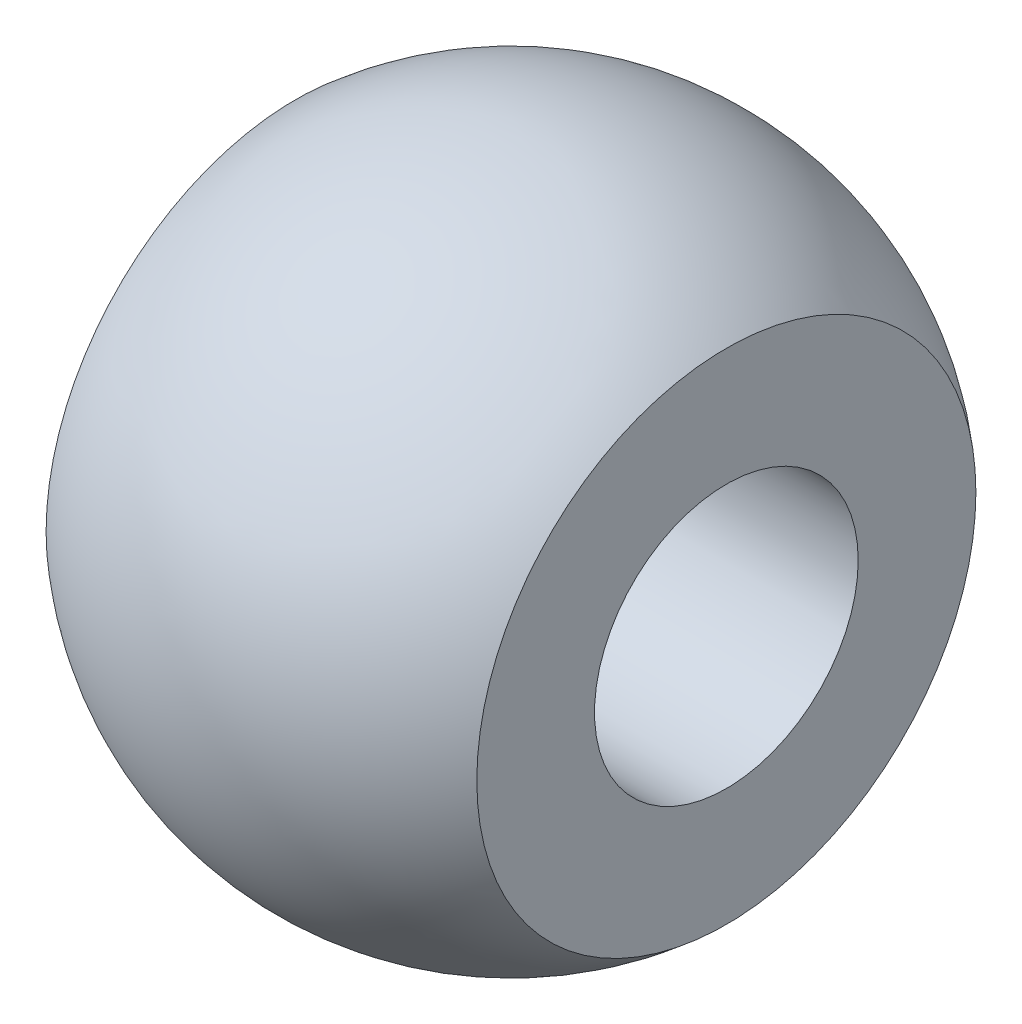
SolidWorks part; units mm, degrees
ref_plane "Front" through (0, 0, 0) normal (0, 0, 1) x (1, 0, 0)
ref_plane "Top" through (0, 0, 0) normal (0, 1, 0) x (1, 0, 0)
ref_plane "Right" through (0, 0, 0) normal (1, 0, 0) x (0, 0, -1)
sketch "Sketch4" plane through (0, 0, 0) normal (1, 0, 0) x (0, 0, -1)
  line L0 (-3.4269, 1.5227) -> (3.4269, -1.5227)
  arc A0 (-3.4269, 1.5227) -> (3.4269, -1.5227) centre (0, 0) ccw
  dimension "D1" = 7.5
revolve "Revolve1" add sketch "Sketch4" angle 360 about L0
sketch "Sketch5" plane through (0, 0, 0) normal (0, 1, 0) x (1, 0, 0)
  line L0 (0, -5.173) -> (0, 6.106) construction
  line L1 (-7.0321, 4.9864) -> (-2.45, 4.9864)
  line L2 (-7.0321, 4.9864) -> (-7.0321, -5.173)
  line L3 (-7.0321, -5.173) -> (-2.45, -5.173)
  line L4 (-2.45, 4.9864) -> (-2.45, -5.173)
  line L9 (6.0369, 4.9864) -> (2.45, 4.9864)
  line L10 (6.0369, 4.9864) -> (6.0369, -5.173)
  line L11 (6.0369, -5.173) -> (2.45, -5.173)
  line L12 (2.45, 4.9864) -> (2.45, -5.173)
  dimension "D1" = 4.9
  dimension "D2" = 2.45
extrude "Cut-Extrude1" cut sketch "Sketch5" against normal through all both and the other way through all
sketch "Sketch6" plane through (2.45, 0, 0) normal (1, 0, 0) x (0, 0, -1)
  circle A0 centre (0, 0) radius 1.5
  dimension "D1" = 3
extrude "Cut-Extrude2" cut sketch "Sketch6" against normal up to surface (4.9 mm away) contours A0 up to face at (-2.45, 0, -2.839)
ref_axis "Axis1" through (-2.45, 0, 0) along (1, 0, 0)
ref_plane "Plane1" through (0, 0, 0) normal (1, 0, 0) x (0, 0, -1)
ref_point "Point1"
